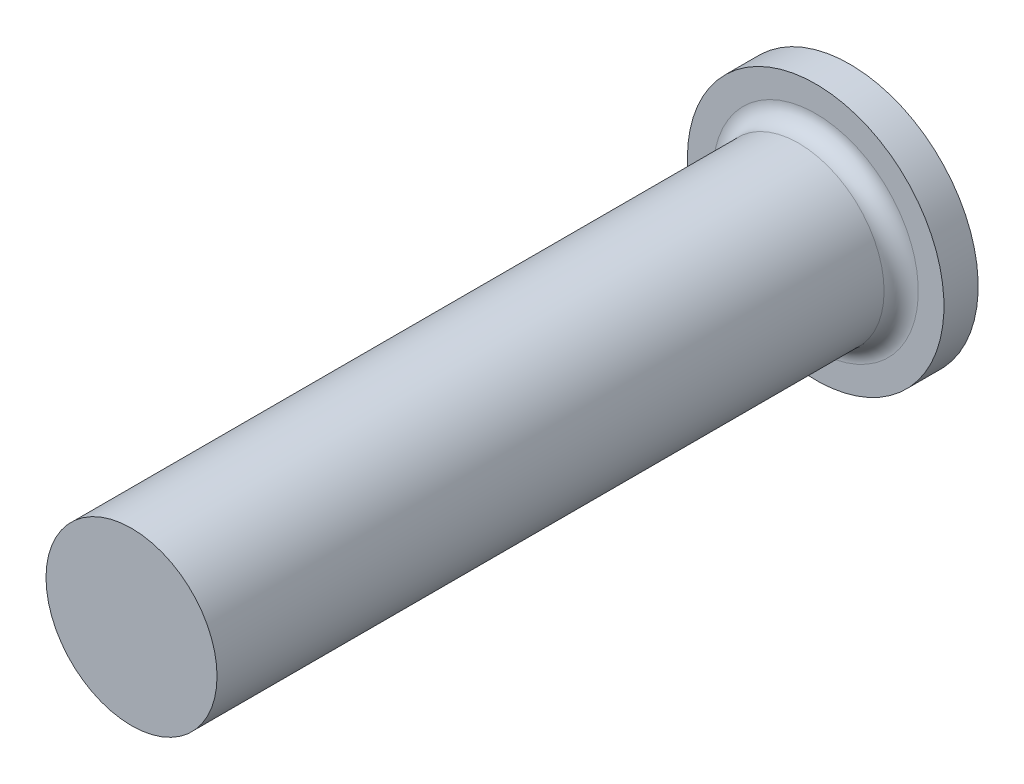
SolidWorks part; units mm, degrees
ref_plane "Alzado" through (0, 0, 0) normal (0, 0, 1) x (1, 0, 0)
ref_plane "Planta" through (0, 0, 0) normal (0, 1, 0) x (1, 0, 0)
ref_plane "Vista lateral" through (0, 0, 0) normal (1, 0, 0) x (0, 0, -1)
sketch "Croquis1" plane through (0, 0, 0) normal (0, 0, 1) x (1, 0, 0)
  circle A0 centre (0, 0) radius 5
  dimension "D1" = 10
extrude "Barras" add sketch "Croquis1" along normal blind 40
sketch "Croquis2" plane through (0, 0, 0) normal (0, 0, -1) x (-1, 0, 0)
  circle A0 centre (0, 0) radius 7.5
  dimension "D1" = 15
extrude "Sujeción" add sketch "Croquis2" along normal blind 2
fillet "Redondeo1" radius 1 1 edges at (5, 0, 0)
